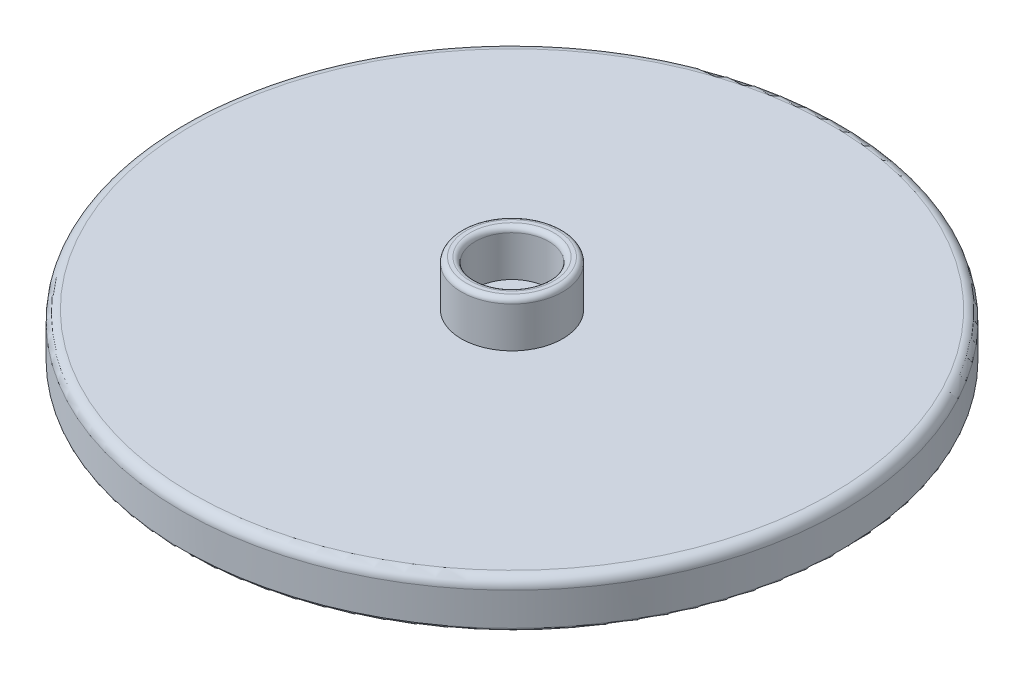
SolidWorks part; units mm, degrees
ref_plane "Front Plane" through (0, 0, 0) normal (0, 0, 1) x (1, 0, 0)
ref_plane "Top Plane" through (0, 0, 0) normal (0, 1, 0) x (1, 0, 0)
ref_plane "Right Plane" through (0, 0, 0) normal (1, 0, 0) x (0, 0, -1)
sketch "Sketch1" plane through (0, 0, 0) normal (0, 1, 0) x (1, 0, 0)
  circle A0 centre (54.1117, 0) radius 65
  dimension "D1" = 130
extrude "Boss-Extrude1" add sketch "Sketch1" along normal blind 9 contours A0
sketch "Sketch2" plane through (0, 9, 0) normal (0, 1, 0) x (1, 0, 0)
  line L0 (-10.8883, 0) -> (119.1117, 0) construction
  circle A0 centre (54.1117, 0) radius 65 construction
  circle A1 centre (54.1117, 0) radius 10
  dimension "D1" = 20
extrude "Boss-Extrude2" add sketch "Sketch2" along normal blind 9
sketch "Sketch3" plane through (0, 18, 0) normal (0, 1, 0) x (1, 0, 0)
  circle A0 centre (54.1117, 0) radius 7.25
  dimension "D1" = 14.5
extrude "Cut-Extrude1" cut sketch "Sketch3" against normal blind 9
sketch "Sketch4" plane through (0, 0, 0) normal (0, -1, 0) x (1, 0, 0)
  line L3 (-21.3999, 1.5) -> (-7.3883, 1.5)
  line L4 (-21.3999, 1.5) -> (-21.3999, -1.5)
  line L5 (-21.3999, -1.5) -> (-7.3883, -1.5)
  line L6 (129.6232, 1.5) -> (129.6232, -1.5)
  line L9 (52.6117, 70.135) -> (55.6117, 70.135)
  line L10 (52.6117, 70.135) -> (52.6117, 61.5)
  line L11 (52.6117, -70.135) -> (55.6117, -70.135)
  line L12 (55.6117, 70.135) -> (55.6117, 61.5)
  line L19 (115.6117, 1.5) -> (129.6232, 1.5)
  line L20 (115.6117, -1.5) -> (129.6232, -1.5)
  line L21 (55.6117, -61.5) -> (55.6117, -70.135)
  line L22 (52.6117, -61.5) -> (52.6117, -70.135)
  arc A0 (115.6117, -1.5) -> (55.6117, -61.5) centre (115.6117, -61.5) ccw
  arc A1 (-7.3883, -1.5) -> (52.6117, -61.5) centre (-7.3883, -61.5) cw
  arc A2 (115.6117, 1.5) -> (55.6117, 61.5) centre (115.6117, 61.5) cw
  arc A3 (-7.3883, 1.5) -> (52.6117, 61.5) centre (-7.3883, 61.5) ccw
  point P2 (55.6117, -1.5)
  point P6 (52.6117, -1.5)
  point P7 (54.1117, 0)
  point P12 (54.1117, 0)
  dimension "D3" = 60
  dimension "D1" = 3
  dimension "D2" = 3
extrude "Cut-Extrude2" cut sketch "Sketch4" against normal blind 0.5
fillet "Fillet1" radius 0.5 16 edges at (117.353, 0, 1.5) (55.6117, 0, 63.2413) (100.0736, 0, 45.9619) (52.6117, 0, 63.2413) (-9.1297, 0, 1.5) (8.1497, 0, 45.9619) (-9.1297, 0, -1.5) (52.6117, 0, -63.2413) (8.1497, 0, -45.9619) (55.6117, 0, -63.2413) (117.353, 0, -1.5) (100.0736, 0, -45.9619) (73.1853, 0, 19.0736) (73.1853, 0, -19.0736) (35.0381, 0, -19.0736) (35.0381, 0, 19.0736)
fillet "Fillet2" radius 2 1 edges at (54.1117, 9, 65)
fillet "Fillet3" radius 1 2 edges at (54.1117, 18, 10) (54.1117, 18, 7.25)
